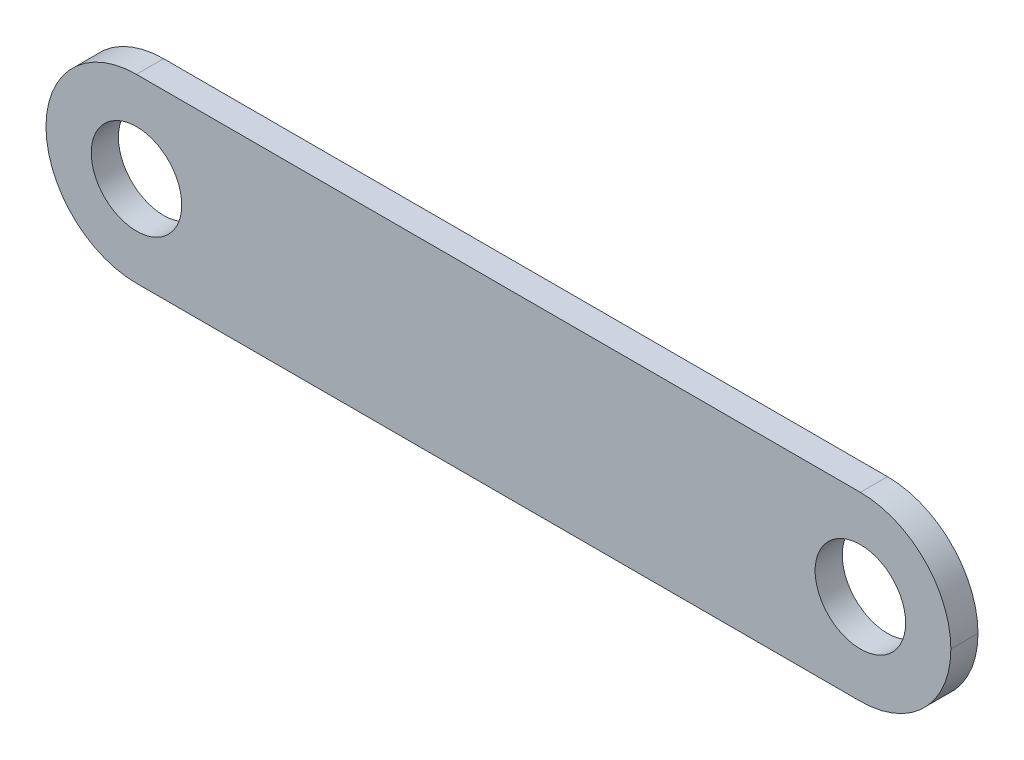
SolidWorks part; units mm, degrees
ref_plane "正面" through (0, 0, 0) normal (0, 0, 1) x (1, 0, 0)
ref_plane "平面" through (0, 0, 0) normal (0, 1, 0) x (1, 0, 0)
ref_plane "右側面" through (0, 0, 0) normal (1, 0, 0) x (0, 0, -1)
sketch "ｽｹｯﾁ1" plane through (0, 0, 0) normal (0, 0, 1) x (1, 0, 0)
  line L1 (0, 0) -> (100, 0)
  line L2 (0, 0) -> (0, 20)
  line L3 (0, 20) -> (100, 20)
  line L4 (100, 0) -> (100, 20)
  dimension "D1" = 100
  dimension "D2" = 20
extrude "ﾎﾞｽ - 押し出し1" add sketch "ｽｹｯﾁ1" along normal blind 3
fillet "ﾌｨﾚｯﾄ1" radius 10 4 edges at (100, 0, 1.5) (100, 20, 1.5) (0, 0, 1.5) (0, 20, 1.5)
sketch "ｽｹｯﾁ2" plane through (0, 0, 3) normal (0, 0, 1) x (1, 0, 0)
  line L0 (10, 0) -> (90, 0) construction
  circle A0 centre (10, 10) radius 5
  circle A1 centre (90, 10) radius 5
  arc A2 (90, 0) -> (100, 10) centre (90, 10) ccw construction
  dimension "D1" = 10
  dimension "D6" = 10
  dimension "D2" = 10
  dimension "D3" = 80
  dimension "D4" = 10
extrude "ｶｯﾄ - 押し出し1" cut sketch "ｽｹｯﾁ2" against normal blind 10
